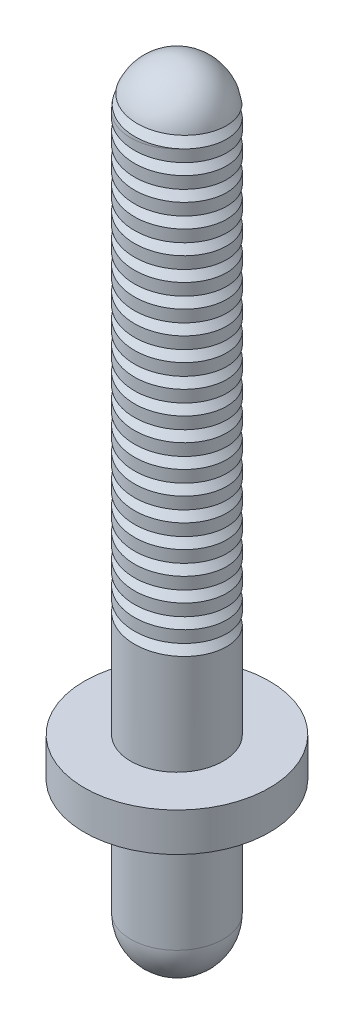
SolidWorks part; units mm, degrees
ref_plane "Front Plane" through (0, 0, 0) normal (0, 0, 1) x (1, 0, 0)
ref_plane "Top Plane" through (0, 0, 0) normal (0, 1, 0) x (1, 0, 0)
ref_plane "Right Plane" through (0, 0, 0) normal (1, 0, 0) x (0, 0, -1)
sketch "Sketch1" plane through (0, 0, 0) normal (0, 0, 1) x (1, 0, 0)
  line L0 (0, 0) -> (0, 120) construction
  line L1 (0, 6) -> (0, -6) construction
  line L2 (-6, 0) -> (-6, 15)
  line L3 (-6, 15) -> (-12, 15)
  line L4 (-12, 15) -> (-12, 20)
  line L5 (-12, 20) -> (-6, 20)
  line L6 (-6, 20) -> (-6, 90)
  line L7 (0, 95.9727) -> (0, -6)
  arc A0 (-6, 90) -> (0, 95.9727) centre (-0.0272, 90) cw
  arc A1 (-6, 0) -> (0, -6) centre (0, 0) ccw
  point P11 (-0.0272, 95.9728)
  point P13 (0, -6)
  point P14 (0, 6)
  dimension "D1" = 6
  dimension "D2" = 15
  dimension "D3" = 12
  dimension "D4" = 5
  dimension "D5" = 70
revolve "Revolve1" add sketch "Sketch1" angle 360 about L7
ref_plane "Plane1" through (0, 32, 0) normal (0, 1, 0) x (1, 0, 0)
sketch "Sketch3" plane through (0, 32, 0) normal (0, 1, 0) x (1, 0, 0)
  circle A0 centre (0, 0) radius 6
  dimension "D1" = 12
curve "Helix/Spiral1" pitch 3 height 60 radius 6 left hand yes centre (0, 32, 0) axis (0, 1, 0) start towards (0, 0, 1)
sketch "Sketch19" plane through (0, 0, 0) normal (0, 0, 1) x (1, 0, 0)
  line L0 (-6, 90) -> (-6, 20) construction
  line L1 (-4.83, 32.2707) -> (-6.83, 32.8595)
  line L2 (-6.83, 32.8595) -> (-6.34, 30.8331)
  line L3 (-6.34, 30.8331) -> (-4.83, 32.2707)
  circle A0 centre (-6, 31.9878) radius 0.6019 construction
  point P7 (-5.984, 32.0064)
  point P8 (-6.2793, 32.5144)
  dimension "D1" = 2
sweep "Cut-Sweep1" cut profiles "Sketch19" path "Helix/Spiral1" align with end faces yes
